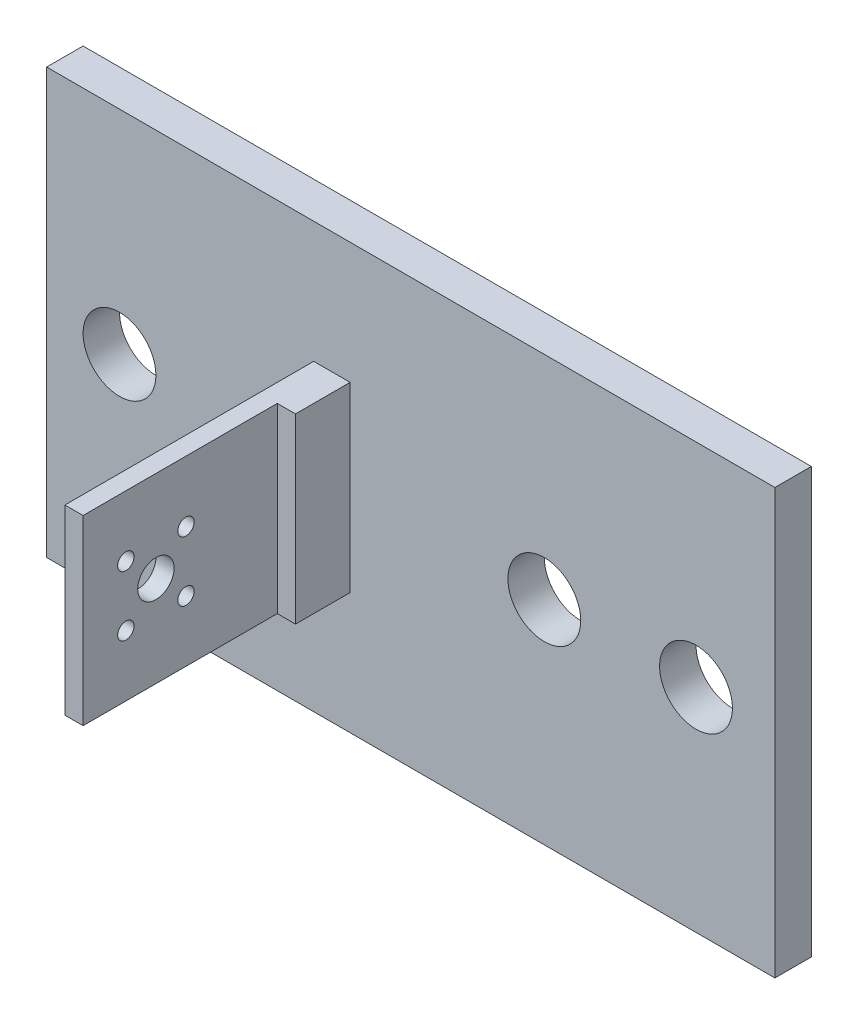
SolidWorks part; units mm, degrees
ref_plane "Front Plane" through (0, 0, 0) normal (0, 0, 1) x (1, 0, 0)
ref_plane "Top Plane" through (0, 0, 0) normal (0, 1, 0) x (1, 0, 0)
ref_plane "Right Plane" through (0, 0, 0) normal (1, 0, 0) x (0, 0, -1)
ref_plane "PZ_m35_000" through (0, 0, -35) normal (0, 0, 1) x (1, 0, 0)
sketch "S_box1" plane through (0, 0, -35) normal (0, 0, 1) x (1, 0, 0)
  line L0 (-62, -35) -> (58, -35)
  line L1 (58, -35) -> (58, 35)
  line L2 (58, 35) -> (-62, 35)
  line L3 (-62, 35) -> (-62, -35)
  dimension "P1" = 62
  dimension "P2" = 35
  dimension "P3" = 58
  dimension "P4" = 35
  dimension "P5" = 58
  dimension "P6" = 35
  dimension "P7" = 62
  dimension "P8" = 35
extrude "Boss_1" add sketch "S_box1" along normal blind 6
ref_plane "PZ_m29_500" through (0, 0, -29.5) normal (0, 0, 1) x (1, 0, 0)
sketch "S_box2" plane through (0, 0, -29.5) normal (0, 0, 1) x (1, 0, 0)
  line L0 (-18, -15) -> (-15, -15)
  line L1 (-15, -15) -> (-15, 15)
  line L2 (-15, 15) -> (-18, 15)
  line L3 (-18, 15) -> (-18, -15)
  dimension "P1" = 18
  dimension "P2" = 15
  dimension "P3" = 15
  dimension "P4" = 15
  dimension "P5" = 15
  dimension "P6" = 15
  dimension "P7" = 18
  dimension "P8" = 15
extrude "Boss_2" add sketch "S_box2" along normal blind 41.5
sketch "S_box3" plane through (0, 0, -29.5) normal (0, 0, 1) x (1, 0, 0)
  line L0 (-15.5, -15) -> (-12, -15)
  line L1 (-12, -15) -> (-12, 15)
  line L2 (-12, 15) -> (-15.5, 15)
  line L3 (-15.5, 15) -> (-15.5, -15)
  dimension "P1" = 15.5
  dimension "P2" = 15
  dimension "P3" = 12
  dimension "P4" = 15
  dimension "P5" = 12
  dimension "P6" = 15
  dimension "P7" = 15.5
  dimension "P8" = 15
extrude "Boss_3" add sketch "S_box3" along normal blind 9.5
ref_plane "PX_m18_100" through (-18.1, 0, 0) normal (1, 0, 0) x (0, 0, -1)
sketch "S_hole4" plane through (-18.1, 0, 0) normal (1, 0, 0) x (0, 0, -1)
  circle A0 centre (0, 0) radius 3
  dimension "D1_S_hole4" = 6
extrude "Hole_4" cut sketch "S_hole4" along normal blind 3.2
sketch "S_hole5" plane through (-18.1, 0, 0) normal (1, 0, 0) x (0, 0, -1)
  circle A0 centre (-4.9497, 4.9497) radius 1.35
  dimension "D1_S_hole5" = 2.7
  dimension "P2" = 4.9497
  dimension "P3" = 4.9497
extrude "Hole_5" cut sketch "S_hole5" along normal blind 3.2
sketch "S_hole6" plane through (-18.1, 0, 0) normal (1, 0, 0) x (0, 0, -1)
  circle A0 centre (-4.9497, -4.9497) radius 1.35
  dimension "D1_S_hole6" = 2.7
  dimension "P2" = 4.9497
  dimension "P3" = 4.9497
extrude "Hole_6" cut sketch "S_hole6" along normal blind 3.2
sketch "S_hole7" plane through (-18.1, 0, 0) normal (1, 0, 0) x (0, 0, -1)
  circle A0 centre (4.9497, -4.9497) radius 1.35
  dimension "D1_S_hole7" = 2.7
  dimension "P2" = 4.9497
  dimension "P3" = 4.9497
extrude "Hole_7" cut sketch "S_hole7" along normal blind 3.2
sketch "S_hole8" plane through (-18.1, 0, 0) normal (1, 0, 0) x (0, 0, -1)
  circle A0 centre (4.9497, 4.9497) radius 1.35
  dimension "D1_S_hole8" = 2.7
  dimension "P2" = 4.9497
  dimension "P3" = 4.9497
extrude "Hole_8" cut sketch "S_hole8" along normal blind 3.2
ref_plane "PZ_m35_100" through (0, 0, -35.1) normal (0, 0, 1) x (1, 0, 0)
sketch "S_hole9" plane through (0, 0, -35.1) normal (0, 0, 1) x (1, 0, 0)
  circle A0 centre (-50, 0) radius 6
  dimension "D1_S_hole9" = 12
  dimension "P2" = 50
extrude "Hole_9" cut sketch "S_hole9" along normal blind 6.2
sketch "S_hole10" plane through (0, 0, -35.1) normal (0, 0, 1) x (1, 0, 0)
  circle A0 centre (-20, 0) radius 6
  dimension "D1_S_hole10" = 12
  dimension "P2" = 20
extrude "Hole_10" cut sketch "S_hole10" along normal blind 6.2
sketch "S_hole11" plane through (0, 0, -35.1) normal (0, 0, 1) x (1, 0, 0)
  circle A0 centre (20, 0) radius 6
  dimension "D1_S_hole11" = 12
  dimension "P2" = 20
extrude "Hole_11" cut sketch "S_hole11" along normal blind 6.2
sketch "S_hole12" plane through (0, 0, -35.1) normal (0, 0, 1) x (1, 0, 0)
  circle A0 centre (45, 0) radius 6
  dimension "D1_S_hole12" = 12
  dimension "P2" = 45
extrude "Hole_12" cut sketch "S_hole12" along normal blind 6.2
equation "\"plate_t\" = 3"
equation "\"clearance\" = 0.4"
